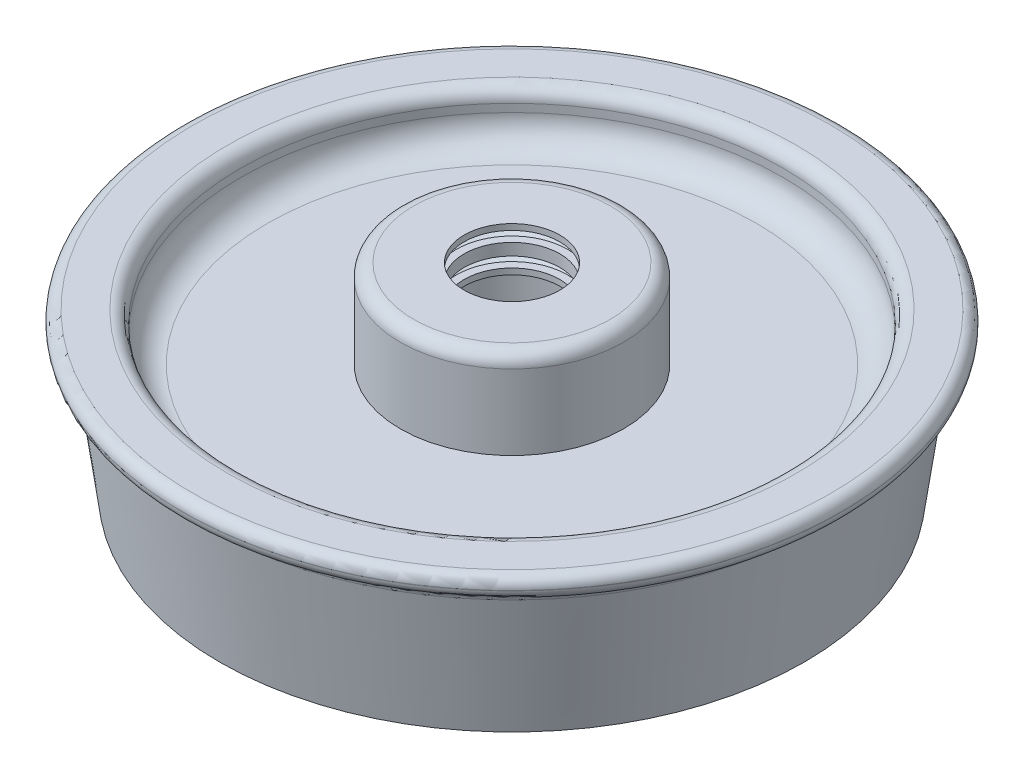
SolidWorks part; units mm, degrees
ref_plane "Alzado" through (0, 0, 0) normal (0, 0, 1) x (1, 0, 0)
ref_plane "Planta" through (0, 0, 0) normal (0, 1, 0) x (1, 0, 0)
ref_plane "Vista lateral" through (0, 0, 0) normal (1, 0, 0) x (0, 0, -1)
sketch "Croquis1" plane through (0, 0, 0) normal (0, 0, 1) x (1, 0, 0)
  line L0 (-102, 42) -> (-102, 60)
  line L2 (-124, 60) -> (-124, 52)
  line L9 (-102, 42) -> (-42, 42)
  line L15 (-124, 60) -> (-102, 60)
  line L18 (-102, 0) -> (-102, 34)
  line L19 (-102, 34) -> (-42, 34)
  line L20 (-42, 42) -> (-42, 75.1957)
  line L21 (-42, 75.1957) -> (-18, 75.1957)
  line L22 (-18, 75.1957) -> (-18, 58.491)
  line L23 (-18, 58.491) -> (-28, 58.491)
  line L24 (-28, 58.491) -> (-28, 12)
  line L25 (-28, 12) -> (-42, 12)
  line L26 (-42, 12) -> (-42, 34)
  line L31 (-124, 52) -> (-117.1816, 52)
  line L34 (-110, 0) -> (-102, 0)
  line L35 (-110, 0) -> (-117.1816, 52)
  line L36 (0, 0) -> (0, 50000) construction
  point P4 (-106, 0)
  dimension "D1" = 106
  dimension "D2" = 18
  dimension "D3" = 22
  dimension "D4" = 14
  dimension "D5" = 8
  dimension "D6" = 106
  dimension "D7" = 60
  dimension "D8" = 0
  dimension "D9" = 28
  dimension "D11" = 117.1816
  dimension "D12" = 12
  dimension "D13" = 34
  dimension "D14" = 58.491
  dimension "D18" = 75.1957
revolve "Revolución1" add sketch "Croquis1" angle 360 about L36
fillet "Redondeo1" radius 5 1 edges at (0, 60, -102)
fillet "Redondeo2" radius 10 1 edges at (0, 42, -102)
fillet "Redondeo3" radius 5 1 edges at (0, 52, -117.1816)
fillet "Redondeo5" radius 4 1 edges at (0, 60, -124)
fillet "Redondeo6" radius 4 1 edges at (0, 52, -124)
fillet "Redondeo7" radius 5 1 edges at (0, 75.1957, -42)
fillet "Redondeo8" radius 10 1 edges at (0, 34, -102)
sketch "Croquis3" plane through (0, 0, 0) normal (0, 0, 1) x (1, 0, 0)
  line L0 (0, 0) -> (0, 50000) construction
  line L1 (20.9189, 64.6102) -> (24, 63.7108)
  line L2 (0, 64.6102) -> (20.9189, 64.6102)
  line L3 (0, 64.6102) -> (0, 60.7218)
  line L4 (0, 60.7218) -> (20.9465, 60.7218)
  line L6 (24, 63.7108) -> (24, 61.7108)
  line L7 (24, 61.7108) -> (20.9465, 60.7218)
  line L8 (35.8394, 75.1957) -> (50035.8394, 75.1957) construction
  line L10 (25.9494, 58.491) -> (50025.9494, 58.491) construction
  line L12 (115.0429, 66.841) -> (-49884.9571, 66.841) construction
  point P10 (24, 62.7108)
  point P16 (0, 62.666)
  dimension "D1" = 24
  dimension "D2" = 2
  dimension "D3" = 58.491
  dimension "D4" = 75.1957
  dimension "D5" = 8.35
  dimension "D6" = 4.175
  dimension "D7" = 20.9189
  dimension "D8" = 20.9465
  dimension "D9" = 60.7218
revolve "Cortar-Revolución1" cut sketch "Croquis3" angle 360 about L0
ref_plane "Plano2" through (0, 66.8433, 0) normal (0, -1, 0) x (-1, 0, 0)
mirror "Simetría1" about plane through (0, 66.8433, 0) normal (0, -1, 0) of "Cortar-Revolución1"
sketch "Croquis4" plane through (0, 0, 0) normal (0, 0, 1) x (1, 0, 0)
  line L0 (42, 34) -> (42, 24)
  line L1 (-42, 34) -> (42, 34) construction
  line L2 (-92, 34) -> (92, 34) construction
  line L3 (102, 24) -> (-102, 24) construction
  line L4 (42, 24) -> (88.8995, 34)
  line L5 (88.8995, 34) -> (42, 34)
  dimension "D1" = 42
  dimension "D2" = 88.8995
extrude "Saliente-Extruir2" add sketch "Croquis4" along normal blind 3 and the other way blind 3 separate body
pattern_circular "MatrizC2" count 4 over 360 about axis through (0, 34, 0) along (0, -1, 0) of bodies 104
